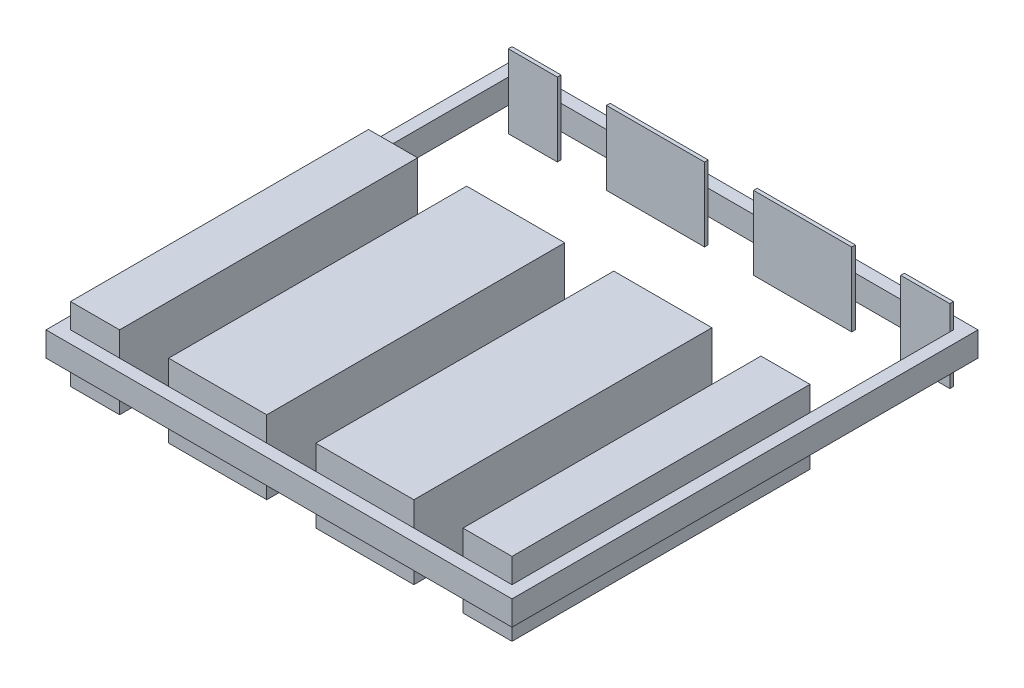
SolidWorks part; units mm, degrees
material "ABS"
ref_plane "Front Plane" through (0, 0, 0) normal (0, 0, 1) x (1, 0, 0)
ref_plane "Top Plane" through (0, 0, 0) normal (0, 1, 0) x (1, 0, 0)
ref_plane "Right Plane" through (0, 0, 0) normal (1, 0, 0) x (0, 0, -1)
sketch "Sketch1" plane through (0, 0, 0) normal (0, 0, 1) x (1, 0, 0)
  line L1 (-90, -15) -> (90, -15)
  line L2 (-90, -15) -> (-90, 15)
  line L3 (-90, 15) -> (90, 15)
  line L4 (90, -15) -> (90, 15)
  line L5 (0, 15) -> (0, -15) construction
  line L6 (-90, 0) -> (90, 0) construction
  point P16 (0, 0)
extrude "Boss-Extrude1" add sketch "Sketch1" along normal mid plane 180
sketch "Sketch2" plane through (0, 0, 0) normal (0, 0, 1) x (1, 0, 0)
  line L0 (-90, -15) -> (90, -15) construction
  line L1 (-70, -15) -> (-50, -15)
  line L2 (-70, -15) -> (-70, 15)
  line L3 (-70, 15) -> (-50, 15)
  line L4 (-50, -15) -> (-50, 15)
  line L5 (-60, 15) -> (-60, -15) construction
  line L6 (-70, 0) -> (-50, 0) construction
  line L7 (90, 15) -> (-90, 15) construction
  line L9 (-10, -15) -> (10, -15)
  line L10 (-10, -15) -> (-10, 15)
  line L11 (-10, 15) -> (10, 15)
  line L12 (10, -15) -> (10, 15)
  line L13 (0, 15) -> (0, -15) construction
  line L14 (-10, 0) -> (10, 0) construction
  line L15 (50, -15) -> (70, -15)
  line L16 (50, -15) -> (50, 15)
  line L17 (50, 15) -> (70, 15)
  line L18 (70, -15) -> (70, 15)
  line L19 (60, 15) -> (60, -15) construction
  line L20 (50, 0) -> (70, 0) construction
  point P20 (-60, 0)
  point P33 (0, 0)
  point P42 (60, 0)
extrude "Cut-Extrude1" cut sketch "Sketch2" against normal mid plane 180
sketch "Sketch3" plane through (0, 0, 0) normal (0, 0, 1) x (1, 0, 0)
  line L1 (-88.5, -13.5) -> (-71.5, -13.5)
  line L2 (-88.5, -13.5) -> (-88.5, 13.5)
  line L3 (-88.5, 13.5) -> (-71.5, 13.5)
  line L4 (-71.5, -13.5) -> (-71.5, 13.5)
  line L5 (-80, 13.5) -> (-80, -13.5) construction
  line L6 (-88.5, 0) -> (-71.5, 0) construction
  line L7 (-48.5, -13.5) -> (-31.5, -13.5)
  line L8 (-48.5, -13.5) -> (-48.5, 13.5)
  line L9 (-48.5, 13.5) -> (-31.5, 13.5)
  line L10 (-31.5, -13.5) -> (-31.5, 13.5)
  line L11 (-40, 13.5) -> (-40, -13.5) construction
  line L12 (-48.5, 0) -> (-31.5, 0) construction
  line L13 (-28.5, -13.5) -> (-11.5, -13.5)
  line L14 (-28.5, -13.5) -> (-28.5, 13.5)
  line L15 (-28.5, 13.5) -> (-11.5, 13.5)
  line L16 (-11.5, -13.5) -> (-11.5, 13.5)
  line L17 (-20, 13.5) -> (-20, -13.5) construction
  line L18 (-28.5, 0) -> (-11.5, 0) construction
  line L19 (11.5, -13.5) -> (28.5, -13.5)
  line L20 (11.5, -13.5) -> (11.5, 13.5)
  line L21 (11.5, 13.5) -> (28.5, 13.5)
  line L22 (28.5, -13.5) -> (28.5, 13.5)
  line L23 (20, 13.5) -> (20, -13.5) construction
  line L24 (11.5, 0) -> (28.5, 0) construction
  line L25 (31.5, -13.5) -> (48.5, -13.5)
  line L26 (31.5, -13.5) -> (31.5, 13.5)
  line L27 (31.5, 13.5) -> (48.5, 13.5)
  line L28 (48.5, -13.5) -> (48.5, 13.5)
  line L29 (40, 13.5) -> (40, -13.5) construction
  line L30 (31.5, 0) -> (48.5, 0) construction
  line L31 (71.5, -13.5) -> (88.5, -13.5)
  line L32 (71.5, -13.5) -> (71.5, 13.5)
  line L33 (71.5, 13.5) -> (88.5, 13.5)
  line L34 (88.5, -13.5) -> (88.5, 13.5)
  line L35 (80, 13.5) -> (80, -13.5) construction
  line L36 (71.5, 0) -> (88.5, 0) construction
  point P16 (-80, 0)
  point P25 (-40, 0)
  point P34 (-20, 0)
  point P43 (20, 0)
  point P52 (40, 0)
  point P61 (80, 0)
extrude "Cut-Extrude2" cut sketch "Sketch3" against normal blind 57 from offset 31.5 flip side to cut offset against normal yes
sketch "Sketch4" plane through (0, 0, 0) normal (0, 0, 1) x (1, 0, 0)
  line L1 (-88.5, -13.5) -> (-71.5, -13.5)
  line L2 (-88.5, -13.5) -> (-88.5, 13.5)
  line L3 (-88.5, 13.5) -> (-71.5, 13.5)
  line L4 (-71.5, -13.5) -> (-71.5, 13.5)
  line L5 (-80, 13.5) -> (-80, -13.5) construction
  line L6 (-88.5, 0) -> (-71.5, 0) construction
  line L7 (-48.5, -13.5) -> (-31.5, -13.5)
  line L8 (-48.5, -13.5) -> (-48.5, 13.5)
  line L9 (-48.5, 13.5) -> (-31.5, 13.5)
  line L10 (-31.5, -13.5) -> (-31.5, 13.5)
  line L11 (-40, 13.5) -> (-40, -13.5) construction
  line L12 (-48.5, 0) -> (-31.5, 0) construction
  line L13 (-28.5, -13.5) -> (-11.5, -13.5)
  line L14 (-28.5, -13.5) -> (-28.5, 13.5)
  line L15 (-28.5, 13.5) -> (-11.5, 13.5)
  line L16 (-11.5, -13.5) -> (-11.5, 13.5)
  line L17 (-20, 13.5) -> (-20, -13.5) construction
  line L18 (-28.5, 0) -> (-11.5, 0) construction
  line L19 (11.5, -13.5) -> (28.5, -13.5)
  line L20 (11.5, -13.5) -> (11.5, 13.5)
  line L21 (11.5, 13.5) -> (28.5, 13.5)
  line L22 (28.5, -13.5) -> (28.5, 13.5)
  line L23 (20, 13.5) -> (20, -13.5) construction
  line L24 (11.5, 0) -> (28.5, 0) construction
  line L25 (31.5, -13.5) -> (48.5, -13.5)
  line L26 (31.5, -13.5) -> (31.5, 13.5)
  line L27 (31.5, 13.5) -> (48.5, 13.5)
  line L28 (48.5, -13.5) -> (48.5, 13.5)
  line L29 (40, 13.5) -> (40, -13.5) construction
  line L30 (31.5, 0) -> (48.5, 0) construction
  line L31 (71.5, -13.5) -> (88.5, -13.5)
  line L32 (71.5, -13.5) -> (71.5, 13.5)
  line L33 (71.5, 13.5) -> (88.5, 13.5)
  line L34 (88.5, -13.5) -> (88.5, 13.5)
  line L35 (80, 13.5) -> (80, -13.5) construction
  line L36 (71.5, 0) -> (88.5, 0) construction
  point P16 (-80, 0)
  point P25 (-40, 0)
  point P34 (-20, 0)
  point P43 (20, 0)
  point P52 (40, 0)
  point P61 (80, 0)
extrude "Cut-Extrude3" cut sketch "Sketch4" against normal mid plane 57
sketch "Sketch5" plane through (0, 0, 0) normal (0, 0, 1) x (1, 0, 0)
  line L1 (-88.5, -13.5) -> (-71.5, -13.5)
  line L2 (-88.5, -13.5) -> (-88.5, 13.5)
  line L3 (-88.5, 13.5) -> (-71.5, 13.5)
  line L4 (-71.5, -13.5) -> (-71.5, 13.5)
  line L5 (-80, 13.5) -> (-80, -13.5) construction
  line L6 (-88.5, 0) -> (-71.5, 0) construction
  line L7 (-48.5, -13.5) -> (-31.5, -13.5)
  line L8 (-48.5, -13.5) -> (-48.5, 13.5)
  line L9 (-48.5, 13.5) -> (-31.5, 13.5)
  line L10 (-31.5, -13.5) -> (-31.5, 13.5)
  line L11 (-40, 13.5) -> (-40, -13.5) construction
  line L12 (-48.5, 0) -> (-31.5, 0) construction
  line L13 (-28.5, -13.5) -> (-11.5, -13.5)
  line L14 (-28.5, -13.5) -> (-28.5, 13.5)
  line L15 (-28.5, 13.5) -> (-11.5, 13.5)
  line L16 (-11.5, -13.5) -> (-11.5, 13.5)
  line L17 (-20, 13.5) -> (-20, -13.5) construction
  line L18 (-28.5, 0) -> (-11.5, 0) construction
  line L19 (11.5, -13.5) -> (28.5, -13.5)
  line L20 (11.5, -13.5) -> (11.5, 13.5)
  line L21 (11.5, 13.5) -> (28.5, 13.5)
  line L22 (28.5, -13.5) -> (28.5, 13.5)
  line L23 (20, 13.5) -> (20, -13.5) construction
  line L24 (11.5, 0) -> (28.5, 0) construction
  line L25 (31.5, -13.5) -> (48.5, -13.5)
  line L26 (31.5, -13.5) -> (31.5, 13.5)
  line L27 (31.5, 13.5) -> (48.5, 13.5)
  line L28 (48.5, -13.5) -> (48.5, 13.5)
  line L29 (40, 13.5) -> (40, -13.5) construction
  line L30 (31.5, 0) -> (48.5, 0) construction
  line L31 (71.5, -13.5) -> (88.5, -13.5)
  line L32 (71.5, -13.5) -> (71.5, 13.5)
  line L33 (71.5, 13.5) -> (88.5, 13.5)
  line L34 (88.5, -13.5) -> (88.5, 13.5)
  line L35 (80, 13.5) -> (80, -13.5) construction
  line L36 (71.5, 0) -> (88.5, 0) construction
  point P16 (-80, 0)
  point P25 (-40, 0)
  point P34 (-20, 0)
  point P43 (20, 0)
  point P52 (40, 0)
  point P61 (80, 0)
extrude "Cut-Extrude4" cut sketch "Sketch5" against normal blind 57 from offset 31.5
sketch "Sketch6" plane through (0, 0, 0) normal (0, 0, 1) x (1, 0, 0)
  line L1 (-76.125, -13.5) -> (-74.625, -13.5)
  line L2 (-76.125, -13.5) -> (-76.125, 11.5)
  line L3 (-76.125, 11.5) -> (-74.625, 11.5)
  line L4 (-74.625, -13.5) -> (-74.625, 11.5)
  line L5 (-75.375, 11.5) -> (-75.375, -13.5) construction
  line L6 (-76.125, -1) -> (-74.625, -1) construction
  line L7 (-80.75, -11.5) -> (-79.25, -11.5)
  line L8 (-80.75, -11.5) -> (-80.75, 13.5)
  line L9 (-80.75, 13.5) -> (-79.25, 13.5)
  line L10 (-79.25, -11.5) -> (-79.25, 13.5)
  line L11 (-80, 13.5) -> (-80, -11.5) construction
  line L12 (-80.75, 1) -> (-79.25, 1) construction
  line L13 (-85.375, -13.5) -> (-83.875, -13.5)
  line L14 (-85.375, -13.5) -> (-85.375, 11.5)
  line L15 (-85.375, 11.5) -> (-83.875, 11.5)
  line L16 (-83.875, -13.5) -> (-83.875, 11.5)
  line L17 (-84.625, 11.5) -> (-84.625, -13.5) construction
  line L18 (-85.375, -1) -> (-83.875, -1) construction
  line L19 (-45.375, -13.5) -> (-43.875, -13.5)
  line L20 (-45.375, -13.5) -> (-45.375, 11.5)
  line L21 (-45.375, 11.5) -> (-43.875, 11.5)
  line L22 (-43.875, -13.5) -> (-43.875, 11.5)
  line L23 (-44.625, 11.5) -> (-44.625, -13.5) construction
  line L24 (-45.375, -1) -> (-43.875, -1) construction
  line L25 (-40.75, -11.5) -> (-39.25, -11.5)
  line L26 (-40.75, -11.5) -> (-40.75, 13.5)
  line L27 (-40.75, 13.5) -> (-39.25, 13.5)
  line L28 (-39.25, -11.5) -> (-39.25, 13.5)
  line L29 (-40, 13.5) -> (-40, -11.5) construction
  line L30 (-40.75, 1) -> (-39.25, 1) construction
  line L31 (-36.125, -13.5) -> (-34.625, -13.5)
  line L32 (-36.125, -13.5) -> (-36.125, 11.5)
  line L33 (-36.125, 11.5) -> (-34.625, 11.5)
  line L34 (-34.625, -13.5) -> (-34.625, 11.5)
  line L35 (-35.375, 11.5) -> (-35.375, -13.5) construction
  line L36 (-36.125, -1) -> (-34.625, -1) construction
  line L37 (-16.125, -13.5) -> (-14.625, -13.5)
  line L38 (-16.125, -13.5) -> (-16.125, 11.5)
  line L39 (-16.125, 11.5) -> (-14.625, 11.5)
  line L40 (-14.625, -13.5) -> (-14.625, 11.5)
  line L41 (-15.375, 11.5) -> (-15.375, -13.5) construction
  line L42 (-16.125, -1) -> (-14.625, -1) construction
  line L43 (-20.75, -11.5) -> (-19.25, -11.5)
  line L44 (-20.75, -11.5) -> (-20.75, 13.5)
  line L45 (-20.75, 13.5) -> (-19.25, 13.5)
  line L46 (-19.25, -11.5) -> (-19.25, 13.5)
  line L47 (-20, 13.5) -> (-20, -11.5) construction
  line L48 (-20.75, 1) -> (-19.25, 1) construction
  line L49 (-25.375, -13.5) -> (-23.875, -13.5)
  line L50 (-25.375, -13.5) -> (-25.375, 11.5)
  line L51 (-25.375, 11.5) -> (-23.875, 11.5)
  line L52 (-23.875, -13.5) -> (-23.875, 11.5)
  line L53 (-24.625, 11.5) -> (-24.625, -13.5) construction
  line L54 (-25.375, -1) -> (-23.875, -1) construction
  line L55 (14.625, -13.5) -> (16.125, -13.5)
  line L56 (14.625, -13.5) -> (14.625, 11.5)
  line L57 (14.625, 11.5) -> (16.125, 11.5)
  line L58 (16.125, -13.5) -> (16.125, 11.5)
  line L59 (15.375, 11.5) -> (15.375, -13.5) construction
  line L60 (14.625, -1) -> (16.125, -1) construction
  line L61 (19.25, -11.5) -> (20.75, -11.5)
  line L62 (19.25, -11.5) -> (19.25, 13.5)
  line L63 (19.25, 13.5) -> (20.75, 13.5)
  line L64 (20.75, -11.5) -> (20.75, 13.5)
  line L65 (20, 13.5) -> (20, -11.5) construction
  line L66 (19.25, 1) -> (20.75, 1) construction
  line L67 (23.875, -13.5) -> (25.375, -13.5)
  line L68 (23.875, -13.5) -> (23.875, 11.5)
  line L69 (23.875, 11.5) -> (25.375, 11.5)
  line L70 (25.375, -13.5) -> (25.375, 11.5)
  line L71 (24.625, 11.5) -> (24.625, -13.5) construction
  line L72 (23.875, -1) -> (25.375, -1) construction
  line L73 (43.875, -13.5) -> (45.375, -13.5)
  line L74 (43.875, -13.5) -> (43.875, 11.5)
  line L75 (43.875, 11.5) -> (45.375, 11.5)
  line L76 (45.375, -13.5) -> (45.375, 11.5)
  line L77 (44.625, 11.5) -> (44.625, -13.5) construction
  line L78 (43.875, -1) -> (45.375, -1) construction
  line L79 (39.25, -11.5) -> (40.75, -11.5)
  line L80 (39.25, -11.5) -> (39.25, 13.5)
  line L81 (39.25, 13.5) -> (40.75, 13.5)
  line L82 (40.75, -11.5) -> (40.75, 13.5)
  line L83 (40, 13.5) -> (40, -11.5) construction
  line L84 (39.25, 1) -> (40.75, 1) construction
  line L85 (34.625, -13.5) -> (36.125, -13.5)
  line L86 (34.625, -13.5) -> (34.625, 11.5)
  line L87 (34.625, 11.5) -> (36.125, 11.5)
  line L88 (36.125, -13.5) -> (36.125, 11.5)
  line L89 (35.375, 11.5) -> (35.375, -13.5) construction
  line L90 (34.625, -1) -> (36.125, -1) construction
  line L91 (74.625, -13.5) -> (76.125, -13.5)
  line L92 (74.625, -13.5) -> (74.625, 11.5)
  line L93 (74.625, 11.5) -> (76.125, 11.5)
  line L94 (76.125, -13.5) -> (76.125, 11.5)
  line L95 (75.375, 11.5) -> (75.375, -13.5) construction
  line L96 (74.625, -1) -> (76.125, -1) construction
  line L97 (79.25, -11.5) -> (80.75, -11.5)
  line L98 (79.25, -11.5) -> (79.25, 13.5)
  line L99 (79.25, 13.5) -> (80.75, 13.5)
  line L100 (80.75, -11.5) -> (80.75, 13.5)
  line L101 (80, 13.5) -> (80, -11.5) construction
  line L102 (79.25, 1) -> (80.75, 1) construction
  line L103 (83.875, -13.5) -> (85.375, -13.5)
  line L104 (83.875, -13.5) -> (83.875, 11.5)
  line L105 (83.875, 11.5) -> (85.375, 11.5)
  line L106 (85.375, -13.5) -> (85.375, 11.5)
  line L107 (84.625, 11.5) -> (84.625, -13.5) construction
  line L108 (83.875, -1) -> (85.375, -1) construction
  point P16 (-75.375, -1)
  point P25 (-80, 1)
  point P34 (-84.625, -1)
  point P43 (-44.625, -1)
  point P52 (-40, 1)
  point P61 (-35.375, -1)
  point P70 (-15.375, -1)
  point P79 (-20, 1)
  point P88 (-24.625, -1)
  point P97 (15.375, -1)
  point P106 (20, 1)
  point P115 (24.625, -1)
  point P124 (44.625, -1)
  point P133 (40, 1)
  point P142 (35.375, -1)
  point P151 (75.375, -1)
  point P160 (80, 1)
  point P169 (84.625, -1)
extrude "Boss-Extrude2" add sketch "Sketch6" along normal blind 57 from offset 31.5 flip side to cut offset against normal yes
sketch "Sketch7" plane through (0, 0, 0) normal (0, 0, 1) x (1, 0, 0)
  line L1 (-76.125, -13.5) -> (-74.625, -13.5)
  line L2 (-76.125, -13.5) -> (-76.125, 11.5)
  line L3 (-76.125, 11.5) -> (-74.625, 11.5)
  line L4 (-74.625, -13.5) -> (-74.625, 11.5)
  line L5 (-75.375, 11.5) -> (-75.375, -13.5) construction
  line L6 (-76.125, -1) -> (-74.625, -1) construction
  line L7 (-80.75, -11.5) -> (-79.25, -11.5)
  line L8 (-80.75, -11.5) -> (-80.75, 13.5)
  line L9 (-80.75, 13.5) -> (-79.25, 13.5)
  line L10 (-79.25, -11.5) -> (-79.25, 13.5)
  line L11 (-80, 13.5) -> (-80, -11.5) construction
  line L12 (-80.75, 1) -> (-79.25, 1) construction
  line L13 (-85.375, -13.5) -> (-83.875, -13.5)
  line L14 (-85.375, -13.5) -> (-85.375, 11.5)
  line L15 (-85.375, 11.5) -> (-83.875, 11.5)
  line L16 (-83.875, -13.5) -> (-83.875, 11.5)
  line L17 (-84.625, 11.5) -> (-84.625, -13.5) construction
  line L18 (-85.375, -1) -> (-83.875, -1) construction
  line L19 (-45.375, -13.5) -> (-43.875, -13.5)
  line L20 (-45.375, -13.5) -> (-45.375, 11.5)
  line L21 (-45.375, 11.5) -> (-43.875, 11.5)
  line L22 (-43.875, -13.5) -> (-43.875, 11.5)
  line L23 (-44.625, 11.5) -> (-44.625, -13.5) construction
  line L24 (-45.375, -1) -> (-43.875, -1) construction
  line L25 (-40.75, -11.5) -> (-39.25, -11.5)
  line L26 (-40.75, -11.5) -> (-40.75, 13.5)
  line L27 (-40.75, 13.5) -> (-39.25, 13.5)
  line L28 (-39.25, -11.5) -> (-39.25, 13.5)
  line L29 (-40, 13.5) -> (-40, -11.5) construction
  line L30 (-40.75, 1) -> (-39.25, 1) construction
  line L31 (-36.125, -13.5) -> (-34.625, -13.5)
  line L32 (-36.125, -13.5) -> (-36.125, 11.5)
  line L33 (-36.125, 11.5) -> (-34.625, 11.5)
  line L34 (-34.625, -13.5) -> (-34.625, 11.5)
  line L35 (-35.375, 11.5) -> (-35.375, -13.5) construction
  line L36 (-36.125, -1) -> (-34.625, -1) construction
  line L37 (-16.125, -13.5) -> (-14.625, -13.5)
  line L38 (-16.125, -13.5) -> (-16.125, 11.5)
  line L39 (-16.125, 11.5) -> (-14.625, 11.5)
  line L40 (-14.625, -13.5) -> (-14.625, 11.5)
  line L41 (-15.375, 11.5) -> (-15.375, -13.5) construction
  line L42 (-16.125, -1) -> (-14.625, -1) construction
  line L43 (-20.75, -11.5) -> (-19.25, -11.5)
  line L44 (-20.75, -11.5) -> (-20.75, 13.5)
  line L45 (-20.75, 13.5) -> (-19.25, 13.5)
  line L46 (-19.25, -11.5) -> (-19.25, 13.5)
  line L47 (-20, 13.5) -> (-20, -11.5) construction
  line L48 (-20.75, 1) -> (-19.25, 1) construction
  line L49 (-25.375, -13.5) -> (-23.875, -13.5)
  line L50 (-25.375, -13.5) -> (-25.375, 11.5)
  line L51 (-25.375, 11.5) -> (-23.875, 11.5)
  line L52 (-23.875, -13.5) -> (-23.875, 11.5)
  line L53 (-24.625, 11.5) -> (-24.625, -13.5) construction
  line L54 (-25.375, -1) -> (-23.875, -1) construction
  line L55 (14.625, -13.5) -> (16.125, -13.5)
  line L56 (14.625, -13.5) -> (14.625, 11.5)
  line L57 (14.625, 11.5) -> (16.125, 11.5)
  line L58 (16.125, -13.5) -> (16.125, 11.5)
  line L59 (15.375, 11.5) -> (15.375, -13.5) construction
  line L60 (14.625, -1) -> (16.125, -1) construction
  line L61 (19.25, -11.5) -> (20.75, -11.5)
  line L62 (19.25, -11.5) -> (19.25, 13.5)
  line L63 (19.25, 13.5) -> (20.75, 13.5)
  line L64 (20.75, -11.5) -> (20.75, 13.5)
  line L65 (20, 13.5) -> (20, -11.5) construction
  line L66 (19.25, 1) -> (20.75, 1) construction
  line L67 (23.875, -13.5) -> (25.375, -13.5)
  line L68 (23.875, -13.5) -> (23.875, 11.5)
  line L69 (23.875, 11.5) -> (25.375, 11.5)
  line L70 (25.375, -13.5) -> (25.375, 11.5)
  line L71 (24.625, 11.5) -> (24.625, -13.5) construction
  line L72 (23.875, -1) -> (25.375, -1) construction
  line L73 (43.875, -13.5) -> (45.375, -13.5)
  line L74 (43.875, -13.5) -> (43.875, 11.5)
  line L75 (43.875, 11.5) -> (45.375, 11.5)
  line L76 (45.375, -13.5) -> (45.375, 11.5)
  line L77 (44.625, 11.5) -> (44.625, -13.5) construction
  line L78 (43.875, -1) -> (45.375, -1) construction
  line L79 (39.25, -11.5) -> (40.75, -11.5)
  line L80 (39.25, -11.5) -> (39.25, 13.5)
  line L81 (39.25, 13.5) -> (40.75, 13.5)
  line L82 (40.75, -11.5) -> (40.75, 13.5)
  line L83 (40, 13.5) -> (40, -11.5) construction
  line L84 (39.25, 1) -> (40.75, 1) construction
  line L85 (34.625, -13.5) -> (36.125, -13.5)
  line L86 (34.625, -13.5) -> (34.625, 11.5)
  line L87 (34.625, 11.5) -> (36.125, 11.5)
  line L88 (36.125, -13.5) -> (36.125, 11.5)
  line L89 (35.375, 11.5) -> (35.375, -13.5) construction
  line L90 (34.625, -1) -> (36.125, -1) construction
  line L91 (74.625, -13.5) -> (76.125, -13.5)
  line L92 (74.625, -13.5) -> (74.625, 11.5)
  line L93 (74.625, 11.5) -> (76.125, 11.5)
  line L94 (76.125, -13.5) -> (76.125, 11.5)
  line L95 (75.375, 11.5) -> (75.375, -13.5) construction
  line L96 (74.625, -1) -> (76.125, -1) construction
  line L97 (79.25, -11.5) -> (80.75, -11.5)
  line L98 (79.25, -11.5) -> (79.25, 13.5)
  line L99 (79.25, 13.5) -> (80.75, 13.5)
  line L100 (80.75, -11.5) -> (80.75, 13.5)
  line L101 (80, 13.5) -> (80, -11.5) construction
  line L102 (79.25, 1) -> (80.75, 1) construction
  line L103 (83.875, -13.5) -> (85.375, -13.5)
  line L104 (83.875, -13.5) -> (83.875, 11.5)
  line L105 (83.875, 11.5) -> (85.375, 11.5)
  line L106 (85.375, -13.5) -> (85.375, 11.5)
  line L107 (84.625, 11.5) -> (84.625, -13.5) construction
  line L108 (83.875, -1) -> (85.375, -1) construction
  point P16 (-75.375, -1)
  point P25 (-80, 1)
  point P34 (-84.625, -1)
  point P43 (-44.625, -1)
  point P52 (-40, 1)
  point P61 (-35.375, -1)
  point P70 (-15.375, -1)
  point P79 (-20, 1)
  point P88 (-24.625, -1)
  point P97 (15.375, -1)
  point P106 (20, 1)
  point P115 (24.625, -1)
  point P124 (44.625, -1)
  point P133 (40, 1)
  point P142 (35.375, -1)
  point P151 (75.375, -1)
  point P160 (80, 1)
  point P169 (84.625, -1)
extrude "Boss-Extrude3" add sketch "Sketch7" along normal mid plane 57
sketch "Sketch8" plane through (0, 0, 0) normal (0, 0, 1) x (1, 0, 0)
  line L1 (-76.125, -13.5) -> (-74.625, -13.5)
  line L2 (-76.125, -13.5) -> (-76.125, 11.5)
  line L3 (-76.125, 11.5) -> (-74.625, 11.5)
  line L4 (-74.625, -13.5) -> (-74.625, 11.5)
  line L5 (-75.375, 11.5) -> (-75.375, -13.5) construction
  line L6 (-76.125, -1) -> (-74.625, -1) construction
  line L7 (-80.75, -11.5) -> (-79.25, -11.5)
  line L8 (-80.75, -11.5) -> (-80.75, 13.5)
  line L9 (-80.75, 13.5) -> (-79.25, 13.5)
  line L10 (-79.25, -11.5) -> (-79.25, 13.5)
  line L11 (-80, 13.5) -> (-80, -11.5) construction
  line L12 (-80.75, 1) -> (-79.25, 1) construction
  line L13 (-85.375, -13.5) -> (-83.875, -13.5)
  line L14 (-85.375, -13.5) -> (-85.375, 11.5)
  line L15 (-85.375, 11.5) -> (-83.875, 11.5)
  line L16 (-83.875, -13.5) -> (-83.875, 11.5)
  line L17 (-84.625, 11.5) -> (-84.625, -13.5) construction
  line L18 (-85.375, -1) -> (-83.875, -1) construction
  line L19 (-45.375, -13.5) -> (-43.875, -13.5)
  line L20 (-45.375, -13.5) -> (-45.375, 11.5)
  line L21 (-45.375, 11.5) -> (-43.875, 11.5)
  line L22 (-43.875, -13.5) -> (-43.875, 11.5)
  line L23 (-44.625, 11.5) -> (-44.625, -13.5) construction
  line L24 (-45.375, -1) -> (-43.875, -1) construction
  line L25 (-40.75, -11.5) -> (-39.25, -11.5)
  line L26 (-40.75, -11.5) -> (-40.75, 13.5)
  line L27 (-40.75, 13.5) -> (-39.25, 13.5)
  line L28 (-39.25, -11.5) -> (-39.25, 13.5)
  line L29 (-40, 13.5) -> (-40, -11.5) construction
  line L30 (-40.75, 1) -> (-39.25, 1) construction
  line L31 (-36.125, -13.5) -> (-34.625, -13.5)
  line L32 (-36.125, -13.5) -> (-36.125, 11.5)
  line L33 (-36.125, 11.5) -> (-34.625, 11.5)
  line L34 (-34.625, -13.5) -> (-34.625, 11.5)
  line L35 (-35.375, 11.5) -> (-35.375, -13.5) construction
  line L36 (-36.125, -1) -> (-34.625, -1) construction
  line L37 (-16.125, -13.5) -> (-14.625, -13.5)
  line L38 (-16.125, -13.5) -> (-16.125, 11.5)
  line L39 (-16.125, 11.5) -> (-14.625, 11.5)
  line L40 (-14.625, -13.5) -> (-14.625, 11.5)
  line L41 (-15.375, 11.5) -> (-15.375, -13.5) construction
  line L42 (-16.125, -1) -> (-14.625, -1) construction
  line L43 (-20.75, -11.5) -> (-19.25, -11.5)
  line L44 (-20.75, -11.5) -> (-20.75, 13.5)
  line L45 (-20.75, 13.5) -> (-19.25, 13.5)
  line L46 (-19.25, -11.5) -> (-19.25, 13.5)
  line L47 (-20, 13.5) -> (-20, -11.5) construction
  line L48 (-20.75, 1) -> (-19.25, 1) construction
  line L49 (-25.375, -13.5) -> (-23.875, -13.5)
  line L50 (-25.375, -13.5) -> (-25.375, 11.5)
  line L51 (-25.375, 11.5) -> (-23.875, 11.5)
  line L52 (-23.875, -13.5) -> (-23.875, 11.5)
  line L53 (-24.625, 11.5) -> (-24.625, -13.5) construction
  line L54 (-25.375, -1) -> (-23.875, -1) construction
  line L55 (14.625, -13.5) -> (16.125, -13.5)
  line L56 (14.625, -13.5) -> (14.625, 11.5)
  line L57 (14.625, 11.5) -> (16.125, 11.5)
  line L58 (16.125, -13.5) -> (16.125, 11.5)
  line L59 (15.375, 11.5) -> (15.375, -13.5) construction
  line L60 (14.625, -1) -> (16.125, -1) construction
  line L61 (19.25, -11.5) -> (20.75, -11.5)
  line L62 (19.25, -11.5) -> (19.25, 13.5)
  line L63 (19.25, 13.5) -> (20.75, 13.5)
  line L64 (20.75, -11.5) -> (20.75, 13.5)
  line L65 (20, 13.5) -> (20, -11.5) construction
  line L66 (19.25, 1) -> (20.75, 1) construction
  line L67 (23.875, -13.5) -> (25.375, -13.5)
  line L68 (23.875, -13.5) -> (23.875, 11.5)
  line L69 (23.875, 11.5) -> (25.375, 11.5)
  line L70 (25.375, -13.5) -> (25.375, 11.5)
  line L71 (24.625, 11.5) -> (24.625, -13.5) construction
  line L72 (23.875, -1) -> (25.375, -1) construction
  line L73 (43.875, -13.5) -> (45.375, -13.5)
  line L74 (43.875, -13.5) -> (43.875, 11.5)
  line L75 (43.875, 11.5) -> (45.375, 11.5)
  line L76 (45.375, -13.5) -> (45.375, 11.5)
  line L77 (44.625, 11.5) -> (44.625, -13.5) construction
  line L78 (43.875, -1) -> (45.375, -1) construction
  line L79 (39.25, -11.5) -> (40.75, -11.5)
  line L80 (39.25, -11.5) -> (39.25, 13.5)
  line L81 (39.25, 13.5) -> (40.75, 13.5)
  line L82 (40.75, -11.5) -> (40.75, 13.5)
  line L83 (40, 13.5) -> (40, -11.5) construction
  line L84 (39.25, 1) -> (40.75, 1) construction
  line L85 (34.625, -13.5) -> (36.125, -13.5)
  line L86 (34.625, -13.5) -> (34.625, 11.5)
  line L87 (34.625, 11.5) -> (36.125, 11.5)
  line L88 (36.125, -13.5) -> (36.125, 11.5)
  line L89 (35.375, 11.5) -> (35.375, -13.5) construction
  line L90 (34.625, -1) -> (36.125, -1) construction
  line L91 (74.625, -13.5) -> (76.125, -13.5)
  line L92 (74.625, -13.5) -> (74.625, 11.5)
  line L93 (74.625, 11.5) -> (76.125, 11.5)
  line L94 (76.125, -13.5) -> (76.125, 11.5)
  line L95 (75.375, 11.5) -> (75.375, -13.5) construction
  line L96 (74.625, -1) -> (76.125, -1) construction
  line L97 (79.25, -11.5) -> (80.75, -11.5)
  line L98 (79.25, -11.5) -> (79.25, 13.5)
  line L99 (79.25, 13.5) -> (80.75, 13.5)
  line L100 (80.75, -11.5) -> (80.75, 13.5)
  line L101 (80, 13.5) -> (80, -11.5) construction
  line L102 (79.25, 1) -> (80.75, 1) construction
  line L103 (83.875, -13.5) -> (85.375, -13.5)
  line L104 (83.875, -13.5) -> (83.875, 11.5)
  line L105 (83.875, 11.5) -> (85.375, 11.5)
  line L106 (85.375, -13.5) -> (85.375, 11.5)
  line L107 (84.625, 11.5) -> (84.625, -13.5) construction
  line L108 (83.875, -1) -> (85.375, -1) construction
  point P16 (-75.375, -1)
  point P25 (-80, 1)
  point P34 (-84.625, -1)
  point P43 (-44.625, -1)
  point P52 (-40, 1)
  point P61 (-35.375, -1)
  point P70 (-15.375, -1)
  point P79 (-20, 1)
  point P88 (-24.625, -1)
  point P97 (15.375, -1)
  point P106 (20, 1)
  point P115 (24.625, -1)
  point P124 (44.625, -1)
  point P133 (40, 1)
  point P142 (35.375, -1)
  point P151 (75.375, -1)
  point P160 (80, 1)
  point P169 (84.625, -1)
extrude "Boss-Extrude4" add sketch "Sketch8" along normal blind 57 from offset 31.5
sketch "Sketch9" plane through (0, 0, 0) normal (0, 0, 1) x (1, 0, 0)
  line L0 (-70, 15) -> (-70, -15) construction
  line L1 (-71.5, -13.5) -> (-70, -13.5)
  line L2 (-71.5, -13.5) -> (-71.5, -11.5)
  line L3 (-71.5, -11.5) -> (-70, -11.5)
  line L4 (-70, -13.5) -> (-70, -11.5)
  line L5 (-70.75, -11.5) -> (-70.75, -13.5) construction
  line L6 (-71.5, -12.5) -> (-70, -12.5) construction
  line L7 (-10, 15) -> (-10, -15) construction
  line L8 (-11.5, -13.5) -> (-10, -13.5)
  line L9 (-11.5, -13.5) -> (-11.5, -12.5)
  line L10 (-11.5, -12.5) -> (-10, -12.5)
  line L11 (-10, -13.5) -> (-10, -12.5)
  line L12 (-10.75, -12.5) -> (-10.75, -13.5) construction
  line L13 (-11.5, -13) -> (-10, -13) construction
  line L14 (10, -15) -> (10, 15) construction
  line L15 (10, -13) -> (11.5, -13)
  line L16 (10, -13) -> (10, -12.5)
  line L17 (10, -12.5) -> (11.5, -12.5)
  line L18 (11.5, -13) -> (11.5, -12.5)
  line L19 (10.75, -12.5) -> (10.75, -13) construction
  line L20 (10, -12.75) -> (11.5, -12.75) construction
  line L21 (50, 15) -> (50, -15) construction
  line L22 (48.5, -12.75) -> (50, -12.75)
  line L23 (48.5, -12.75) -> (48.5, -12.5)
  line L24 (48.5, -12.5) -> (50, -12.5)
  line L25 (50, -12.75) -> (50, -12.5)
  line L26 (49.25, -12.5) -> (49.25, -12.75) construction
  line L27 (48.5, -12.625) -> (50, -12.625) construction
  point P20 (-70.75, -12.5)
  point P31 (-10.75, -13)
  point P38 (10.75, -12.75)
  point P53 (49.25, -12.625)
extrude "Cut-Extrude5" cut sketch "Sketch9" against normal blind 57 from offset 31.5 flip side to cut offset against normal yes
sketch "Sketch10" plane through (0, 0, 0) normal (0, 0, 1) x (1, 0, 0)
  line L0 (-70, 15) -> (-70, -15) construction
  line L1 (-71.5, -13.5) -> (-70, -13.5)
  line L2 (-71.5, -13.5) -> (-71.5, -11.5)
  line L3 (-71.5, -11.5) -> (-70, -11.5)
  line L4 (-70, -13.5) -> (-70, -11.5)
  line L5 (-70.75, -11.5) -> (-70.75, -13.5) construction
  line L6 (-71.5, -12.5) -> (-70, -12.5) construction
  line L7 (-10, 15) -> (-10, -15) construction
  line L8 (-11.5, -13.5) -> (-10, -13.5)
  line L9 (-11.5, -13.5) -> (-11.5, -12.5)
  line L10 (-11.5, -12.5) -> (-10, -12.5)
  line L11 (-10, -13.5) -> (-10, -12.5)
  line L12 (-10.75, -12.5) -> (-10.75, -13.5) construction
  line L13 (-11.5, -13) -> (-10, -13) construction
  line L14 (10, -15) -> (10, 15) construction
  line L15 (10, -13) -> (11.5, -13)
  line L16 (10, -13) -> (10, -12.5)
  line L17 (10, -12.5) -> (11.5, -12.5)
  line L18 (11.5, -13) -> (11.5, -12.5)
  line L19 (10.75, -12.5) -> (10.75, -13) construction
  line L20 (10, -12.75) -> (11.5, -12.75) construction
  line L21 (50, 15) -> (50, -15) construction
  line L22 (48.5, -12.75) -> (50, -12.75)
  line L23 (48.5, -12.75) -> (48.5, -12.5)
  line L24 (48.5, -12.5) -> (50, -12.5)
  line L25 (50, -12.75) -> (50, -12.5)
  line L26 (49.25, -12.5) -> (49.25, -12.75) construction
  line L27 (48.5, -12.625) -> (50, -12.625) construction
  point P20 (-70.75, -12.5)
  point P31 (-10.75, -13)
  point P38 (10.75, -12.75)
  point P53 (49.25, -12.625)
extrude "Cut-Extrude6" cut sketch "Sketch10" against normal mid plane 57
sketch "Sketch11" plane through (0, 0, 0) normal (0, 0, 1) x (1, 0, 0)
  line L0 (-70, 15) -> (-70, -15) construction
  line L1 (-71.5, -13.5) -> (-70, -13.5)
  line L2 (-71.5, -13.5) -> (-71.5, -11.5)
  line L3 (-71.5, -11.5) -> (-70, -11.5)
  line L4 (-70, -13.5) -> (-70, -11.5)
  line L5 (-70.75, -11.5) -> (-70.75, -13.5) construction
  line L6 (-71.5, -12.5) -> (-70, -12.5) construction
  line L7 (-10, 15) -> (-10, -15) construction
  line L8 (-11.5, -13.5) -> (-10, -13.5)
  line L9 (-11.5, -13.5) -> (-11.5, -12.5)
  line L10 (-11.5, -12.5) -> (-10, -12.5)
  line L11 (-10, -13.5) -> (-10, -12.5)
  line L12 (-10.75, -12.5) -> (-10.75, -13.5) construction
  line L13 (-11.5, -13) -> (-10, -13) construction
  line L14 (50, 15) -> (50, -15) construction
  line L15 (10, -13) -> (11.5, -13)
  line L16 (10, -13) -> (10, -12.5)
  line L17 (10, -12.5) -> (11.5, -12.5)
  line L18 (11.5, -13) -> (11.5, -12.5)
  line L19 (10.75, -12.5) -> (10.75, -13) construction
  line L20 (10, -12.75) -> (11.5, -12.75) construction
  line L21 (48.5, -12.75) -> (50, -12.75)
  line L22 (48.5, -12.75) -> (48.5, -12.5)
  line L23 (48.5, -12.5) -> (50, -12.5)
  line L24 (50, -12.75) -> (50, -12.5)
  line L25 (49.25, -12.5) -> (49.25, -12.75) construction
  line L26 (48.5, -12.625) -> (50, -12.625) construction
  point P20 (-70.75, -12.5)
  point P31 (-10.75, -13)
  point P38 (10.75, -12.75)
  point P52 (49.25, -12.625)
extrude "Cut-Extrude7" cut sketch "Sketch11" against normal blind 57 from offset 31.5
sketch "Sketch12" plane through (0, 0, 0) normal (0, 1, 0) x (1, 0, 0)
  line L1 (-95, -95) -> (95, -95)
  line L2 (-95, -95) -> (-95, 95)
  line L3 (-95, 95) -> (95, 95)
  line L4 (95, -95) -> (95, 95)
  line L5 (0, 95) -> (0, -95) construction
  line L6 (-95, 0) -> (95, 0) construction
  line L7 (-90, -90) -> (90, -90)
  line L8 (-90, -90) -> (-90, 90)
  line L9 (-90, 90) -> (90, 90)
  line L10 (90, -90) -> (90, 90)
  line L11 (0, 90) -> (0, -90) construction
  line L12 (-90, 0) -> (90, 0) construction
  point P16 (0, 0)
  point P29 (0, 0)
extrude "Boss-Extrude5" add sketch "Sketch12" along normal mid plane 10
